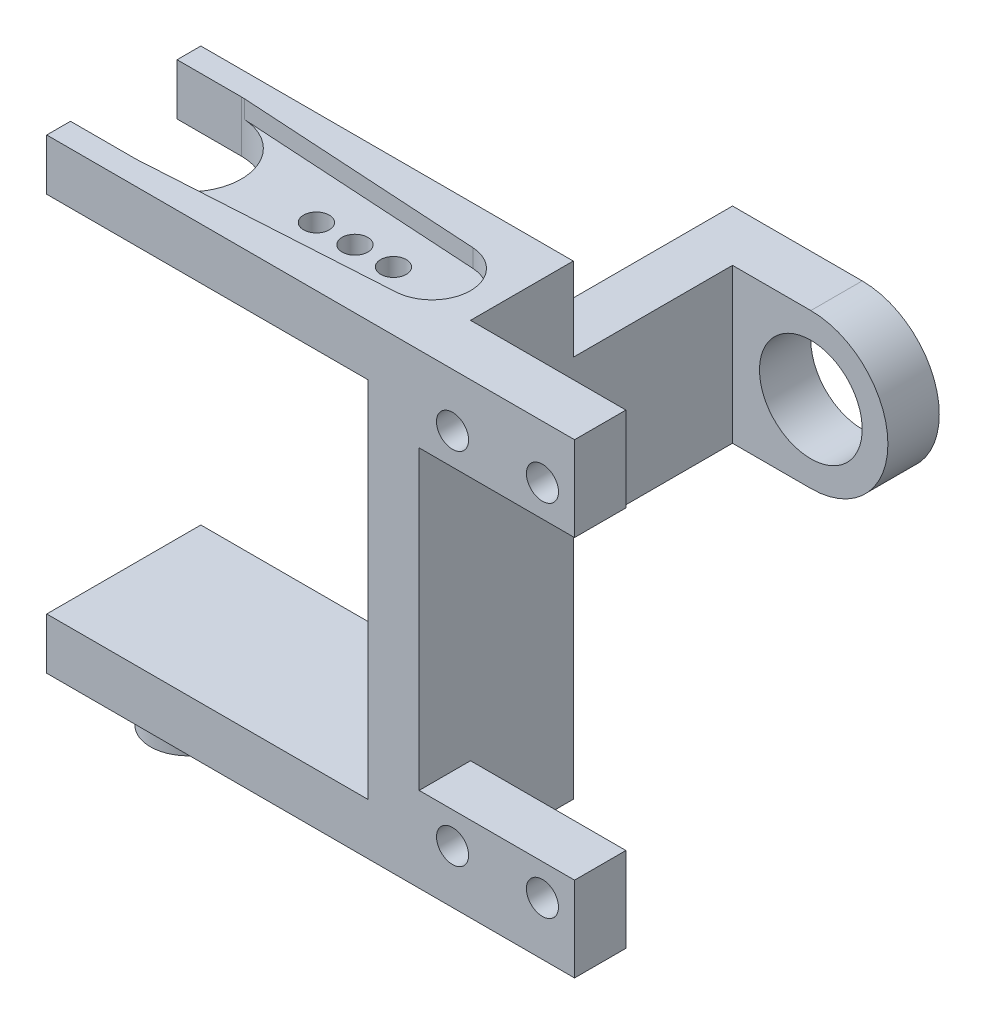
SolidWorks part; units mm, degrees
note: The reader was unsure of these and kept them because the rebuilt part matched: shared geometry of "草图8<3>".
ref_plane "前视基准面" through (0, 0, 0) normal (0, 0, 1) x (1, 0, 0)
ref_plane "上视基准面" through (0, 0, 0) normal (0, 1, 0) x (1, 0, 0)
ref_plane "右视基准面" through (0, 0, 0) normal (1, 0, 0) x (0, 0, -1)
other "Configuration Table"
sketch "草图1" plane through (0, 0, 0) normal (0, 0, 1) x (1, 0, 0)
  line L0 (0, 0) -> (25, 0)
  line L1 (25, 0) -> (25, 28.3)
  line L2 (25, 28.3) -> (0, 28.3)
  line L3 (0, 28.3) -> (0, 0) construction
  line L4 (0, -4) -> (29, -4)
  line L5 (29, -4) -> (29, 32.3)
  line L6 (29, 32.3) -> (0, 32.3)
  line L7 (0, -4) -> (0, 0)
  line L8 (0, 32.3) -> (0, 28.3)
  dimension "D1" = 25
  dimension "D2" = 28.3
  dimension "D3" = 4
extrude "凸台-拉伸1" add sketch "草图1" along normal blind 12
sketch "草图2" plane through (0, -4, 0) normal (0, -1, 0) x (1, 0, 0)
  line L0 (0, 6) -> (5, 6) construction
  line L1 (0, 12) -> (0, 0) construction
  circle A0 centre (5, 6) radius 2.925
  dimension "D1" = 5.85
  dimension "D2" = 5
extrude "凸台-拉伸2" add sketch "草图2" along normal blind 4
sketch "草图3" plane through (0, 0, 12) normal (0, 0, 1) x (1, 0, 0)
  line L0 (29, 14.15) -> (35.1, 14.15) construction
  line L1 (29, -4) -> (29, 32.3) construction
  line L2 (35.1, 0.15) -> (35.1, 28.15) construction
  line L3 (35.1, 28.15) -> (31.6, 28.15) construction
  line L4 (29, 32.3) -> (41.1, 32.3)
  line L5 (41.1, 32.3) -> (41.1, 25.7)
  line L6 (41.1, 25.7) -> (29, 25.7)
  line L7 (29, 25.7) -> (29, 32.3)
  line L8 (35.1, 0.15) -> (31.6, 0.15) construction
  line L9 (29, 2.6) -> (29, -4)
  line L10 (41.1, 2.6) -> (29, 2.6)
  line L11 (41.1, -4) -> (41.1, 2.6)
  line L12 (29, -4) -> (41.1, -4)
  circle A0 centre (31.6, 28.15) radius 1.25
  circle A1 centre (38.6, 28.15) radius 1.25
  circle A2 centre (38.6, 0.15) radius 1.25
  circle A3 centre (31.6, 0.15) radius 1.25
  dimension "D3" = 2.5
  dimension "D1" = 6.1
  dimension "D2" = 28
  dimension "D4" = 7
  dimension "D5" = 12.1
  dimension "D6" = 2.45
extrude "凸台-拉伸3" add sketch "草图3" against normal blind 4
sketch "草图4" plane through (29, 0, 0) normal (1, 0, 0) x (0, 0, -1)
  line L0 (0, -4) -> (0, 32.3) construction
  line L1 (0, -4) -> (0, 32.3) construction
  line L2 (0, 19.81) -> (12.4, 19.81) construction
  line L3 (0, 13.81) -> (12.4, 13.81)
  line L4 (0, 25.81) -> (12.4, 25.81)
  line L5 (0, 25.81) -> (0, 13.81)
  line L6 (12.4, 25.81) -> (12.4, 13.81)
  point P4 (0, 14.15)
  dimension "D1" = 5.66
  dimension "D2" = 12.4
  dimension "D3" = 6
  dimension "D4" = 6
extrude "凸台-拉伸4" add sketch "草图4" against normal blind 4
sketch "草图5" plane through (0, 0, -12.4) normal (0, 0, -1) x (-1, 0, 0)
  line L0 (-29, 19.81) -> (-35.1, 19.81) construction
  line L1 (-29, 13.81) -> (-29, 25.81) construction
  line L2 (-35.1, 25.81) -> (-29, 25.81)
  line L3 (-29, 32.3) -> (-29, 25.7) construction
  line L4 (-29, 25.81) -> (-29, 19.81)
  line L5 (-35.1, 13.81) -> (-29, 13.81)
  line L6 (-29, 13.81) -> (-29, 19.81)
  circle A0 centre (-35.1, 19.81) radius 6
  dimension "D2" = 12
  dimension "D1" = 6.1
extrude "凸台-拉伸5" add sketch "草图5" along normal blind 4
sketch "草图6" plane through (0, 0, -16.4) normal (0, 0, -1) x (-1, 0, 0)
  circle A0 centre (-35.1, 19.81) radius 4
  dimension "D1" = 8
extrude "切除-拉伸1" cut sketch "草图6" against normal blind 4
sketch "草图7" plane through (0, 32.3, 0) normal (0, 1, 0) x (1, 0, 0)
  line L0 (0, -6) -> (5, -6) construction
  line L1 (0, -12) -> (0, 0) construction
  line L2 (5, -1.85) -> (0, -1.85)
  line L3 (0, -1.85) -> (0, -10.15)
  line L4 (5, -10.15) -> (0, -10.15)
  circle A0 centre (5, -6) radius 4.15
  dimension "D1" = 8.3
  dimension "D2" = 5
extrude "切除-拉伸2" cut sketch "草图7" against normal blind 4
sketch "草图8" plane through (0, 32.3, 0) normal (0, 1, 0) x (1, 0, 0)
  line L0 (5, -6) -> (24, -6) construction
  line L1 (5.2512, -1.8576) -> (24.1816, -3.0055)
  line L2 (5.2512, -10.1424) -> (24.1816, -8.9945)
  arc A0 (5, -10.15) -> (5, -1.85) centre (5, -6) ccw construction
  arc A1 (5, -10.15) -> (5, -1.85) centre (5, -6) ccw
  circle A2 centre (24, -6) radius 3
  circle A3 centre (15, -6) radius 1
  circle A4 centre (18, -6) radius 1
  circle A5 centre (21, -6) radius 1
  circle A6 centre (24, -6) radius 1
  dimension "D1" = 6
  dimension "D3" = 2
  dimension "D4" = 2
  dimension "D5" = 2
  dimension "D9" = 2
  dimension "D2" = 19
  dimension "D6" = 10
  dimension "D7" = 3
  dimension "D8" = 3
extrude "切除-拉伸3" cut sketch "草图8" against normal blind 1.4
extrude "切除-拉伸4" cut sketch "草图8<3>" against normal blind 4 contours L0 A3 | A3 L0 | L0 A4 | A4 L0 | A5 L0 A2 | L0 A5 A2 | L0 A2 A5 | A2 L0 A5
sketch "草图8<3>" plane through (0, 32.3, 0) normal (0, 1, 0) x (1, 0, 0) same geometry as "草图8"
sketch "草图9" plane through (0, -8, 0) normal (0, -1, 0) x (1, 0, 0)
  circle A0 centre (4.9981, 6.0065) radius 1.5
  dimension "D1" = 3
extrude "切除-拉伸5" cut sketch "草图9" against normal blind 5
ref_plane "基准面2" through (-10, 0, 0) normal (-1, 0, 0) x (0, 0, 1)
